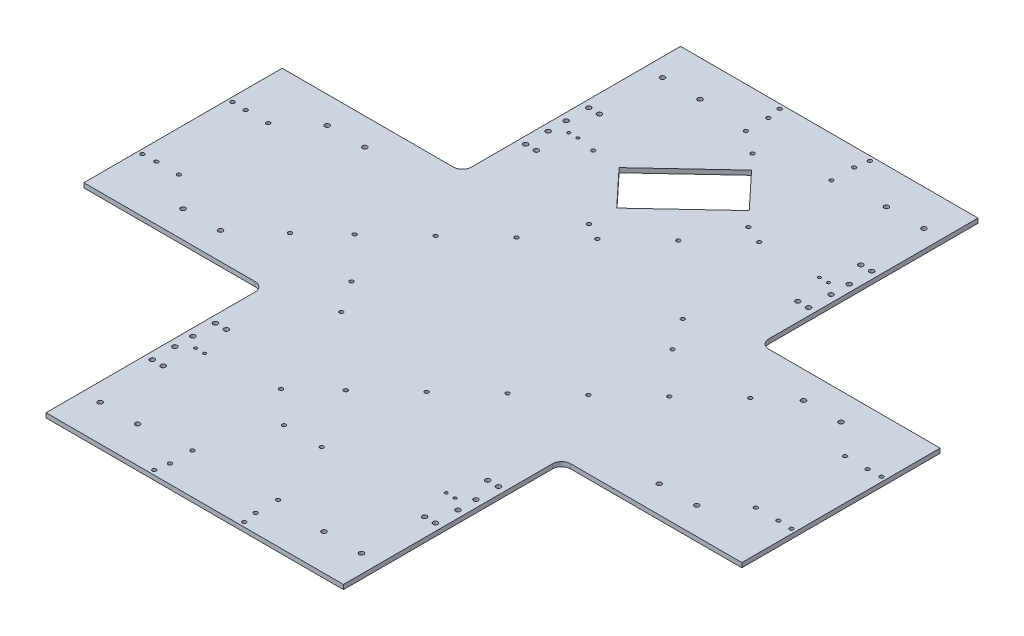
SolidWorks part; units mm, degrees
other "Markup1"
sketch "Sketch8"
material "3.0205 (EN-AW 1200)"
ref_plane "前视基准面" through (0, 0, 0) normal (0, 0, 1) x (1, 0, 0)
ref_plane "上视基准面" through (0, 0, 0) normal (0, 1, 0) x (1, 0, 0)
ref_plane "右视基准面" through (0, 0, 0) normal (1, 0, 0) x (0, 0, -1)
other "Configuration Table"
sketch "Sketch1" plane through (0, 0, 0) normal (0, 1, 0) x (1, 0, 0)
  line L0 (165, 352) -> (-165, 352)
  line L1 (-165, 352) -> (-165, 110)
  line L2 (-165, 110) -> (-365, 110)
  line L5 (-365, 110) -> (-365, -110)
  line L6 (0, 352) -> (0, -66.8675) construction
  line L7 (-365, 0) -> (131.0517, 0) construction
  line L8 (365, 110) -> (365, -110)
  line L11 (165, 110) -> (365, 110)
  line L12 (165, 352) -> (165, 110)
  line L13 (165, -352) -> (165, -110)
  line L14 (165, -110) -> (365, -110)
  line L19 (-165, -110) -> (-365, -110)
  line L20 (-165, -352) -> (-165, -110)
  line L21 (165, -352) -> (-165, -352)
  point P21 (365, 0)
  dimension "D1" = 165
  dimension "D2" = 200
  dimension "D3" = 110
  dimension "D4" = 242
extrude "Boss-Extrude1" add sketch "Sketch1" along normal blind 5
sketch "Sketch2" plane through (0, 5, 0) normal (0, 1, 0) x (1, 0, 0)
  line L3 (365, -110) -> (365, 110) construction
  line L4 (-56.7455, 0) -> (47.5165, 0) construction
  line L5 (0, 54.7142) -> (0, -64.2255) construction
  line L7 (165, 352) -> (-165, 352) construction
  circle A0 centre (345, 49.5) radius 2.125
  circle A1 centre (320, 49.5) radius 2.125
  circle A7 centre (320, -49.5) radius 2.125
  circle A8 centre (345, -49.5) radius 2.125
  circle A9 centre (-345, -49.5) radius 2.125
  circle A10 centre (-320, -49.5) radius 2.125
  circle A13 centre (-320, 49.5) radius 2.125
  circle A14 centre (-345, 49.5) radius 2.125
  circle A15 centre (47.5, 332) radius 2.125
  circle A16 centre (47.5, 307) radius 2.125
  circle A17 centre (-47.5, 307) radius 2.125
  circle A18 centre (-47.5, 332) radius 2.125
  circle A19 centre (-47.5, -332) radius 2.125
  circle A20 centre (-47.5, -307) radius 2.125
  circle A21 centre (47.5, -307) radius 2.125
  circle A22 centre (47.5, -332) radius 2.125
  dimension "D3" = 49.5
  dimension "D5" = 4.25
  dimension "D7" = 4.25
  dimension "D9" = 4.25
  dimension "D10" = 4.25
  dimension "D2" = 47.5
  dimension "D4" = 25
  dimension "D6" = 20
  dimension "20" = 20
  dimension "D13" = 25
extrude "Cut-Extrude1" cut sketch "Sketch2" against normal blind 3
sketch "Sketch4" plane through (0, 5, 0) normal (0, 1, 0) x (1, 0, 0)
  line L0 (-165, 352) -> (-165, 110) construction
  line L1 (165, 352) -> (-165, 352) construction
  line L2 (0, 46.9886) -> (0, -40.2904) construction
  line L3 (-35.103, 0) -> (92.4951, 0) construction
  line L5 (165, -352) -> (165, -110) construction
  circle A0 centre (-157, 172) radius 2.6
  circle A1 centre (-145, 172) radius 2.6
  circle A2 centre (-157, 197) radius 2.6
  circle A3 centre (-157, 217) radius 2.6
  circle A4 centre (-157, 242) radius 2.6
  circle A5 centre (-145, 242) radius 2.6
  circle A6 centre (145, 242) radius 2.6
  circle A7 centre (157, 242) radius 2.6
  circle A8 centre (157, 217) radius 2.6
  circle A9 centre (157, 197) radius 2.6
  circle A10 centre (145, 172) radius 2.6
  circle A11 centre (157, 172) radius 2.6
  circle A12 centre (157, -172) radius 2.6
  circle A13 centre (145, -172) radius 2.6
  circle A14 centre (157, -197) radius 2.6
  circle A15 centre (157, -217) radius 2.6
  circle A16 centre (157, -242) radius 2.6
  circle A17 centre (145, -242) radius 2.6
  circle A18 centre (-145, -242) radius 2.6
  circle A19 centre (-157, -242) radius 2.6
  circle A20 centre (-157, -217) radius 2.6
  circle A21 centre (-157, -197) radius 2.6
  circle A22 centre (-145, -172) radius 2.6
  circle A23 centre (-157, -172) radius 2.6
  circle A24 centre (144, -207) radius 1.6
  circle A25 centre (-144, -207) radius 1.6
  circle A26 centre (144, 207) radius 1.6
  circle A27 centre (-144, 207) radius 1.6
  circle A28 centre (134, -207) radius 1.6
  circle A29 centre (-134, -207) radius 1.6
  circle A30 centre (134, 207) radius 1.6
  circle A31 centre (-134, 207) radius 1.6
  dimension "D3" = 5.2
  dimension "D4" = 5.2
  dimension "D5" = 8
  dimension "D6" = 8
  dimension "D9" = 5.2
  dimension "D10" = 5.2
  dimension "D11" = 5.2
  dimension "D12" = 5.2
  dimension "D19" = 3.2
  dimension "D20" = 21
  dimension "D21" = 10
  dimension "D22" = 3.2
  dimension "D23" = 10
  dimension "D1" = 8
  dimension "D2" = 20
  dimension "D7" = 8
  dimension "D8" = 20
  dimension "D13" = 25
  dimension "D14" = 20
  dimension "D15" = 25
  dimension "D16" = 25
  dimension "D17" = 110
  dimension "D18" = 0
extrude "Cut-Extrude3" cut sketch "Sketch4" against normal blind 10
sketch "Sketch5" plane through (0, 5, 0) normal (0, 1, 0) x (1, 0, 0)
  line L0 (165, 352) -> (-165, 352) construction
  line L5 (-46.9195, 0) -> (66.6223, 0) construction
  line L6 (0, 59.0569) -> (0, -54.4849) construction
  line L10 (-365, 110) -> (-365, -110) construction
  circle A0 centre (-50, 347) radius 2.125
  circle A1 centre (50, 347) radius 2.125
  circle A2 centre (50, -347) radius 2.125
  circle A3 centre (-50, -347) radius 2.125
  circle A4 centre (-360, 50) radius 2.125
  circle A5 centre (-360, -50) radius 2.125
  circle A6 centre (360, -50) radius 2.125
  circle A7 centre (360, 50) radius 2.125
  dimension "D1" = 4.25
  dimension "D2" = 4.25
  dimension "D3" = 50
  dimension "D6" = 4.25
  dimension "D7" = 4.25
  dimension "5" = 5
  dimension "D4" = 50
  dimension "D5" = 50
  dimension "D8" = 50
  dimension "D9" = 5
  dimension "D10" = 5
extrude "Cut-Extrude4" cut sketch "Sketch5" against normal blind 10
fillet "Fillet1" radius 10 4 edges at (-165, 2.5, -110) (-165, 2.5, 110) (165, 2.5, 110) (165, 2.5, -110)
sketch "Sketch6" plane through (0, 5, 0) normal (0, 1, 0) x (1, 0, 0)
  line L0 (165, 352) -> (-165, 352) construction
  line L1 (-165, 352) -> (-165, 120) construction
  line L3 (0, 50.3702) -> (0, -42.7646) construction
  line L4 (-54.8568, 0) -> (91.2004, 0) construction
  line L5 (365, 110) -> (175, 110) construction
  line L6 (365, -110) -> (365, 110) construction
  circle A0 centre (-145, 312) radius 2.6
  circle A1 centre (-103.4, 312) radius 2.6
  circle A4 centre (103.4, 312) radius 2.6
  circle A5 centre (145, 312) radius 2.6
  circle A6 centre (145, -312) radius 2.6
  circle A7 centre (103.4, -312) radius 2.6
  circle A8 centre (-103.4, -312) radius 2.6
  circle A9 centre (-145, -312) radius 2.6
  circle A10 centre (243.4, 80) radius 2.6
  circle A11 centre (285, 80) radius 2.6
  circle A12 centre (285, -80) radius 2.6
  circle A13 centre (243.4, -80) radius 2.6
  circle A14 centre (-243.4, -80) radius 2.6
  circle A15 centre (-285, -80) radius 2.6
  circle A16 centre (-285, 80) radius 2.6
  circle A17 centre (-243.4, 80) radius 2.6
  dimension "D1" = 5.2
  dimension "D2" = 5.2
  dimension "D3" = 5.2
  dimension "D4" = 5.2
  dimension "D5" = 40
  dimension "D8" = 30
  dimension "D6" = 20
  dimension "D7" = 41.6
  dimension "D9" = 80
  dimension "D10" = 41.6
extrude "Cut-Extrude5" cut sketch "Sketch6" against normal blind 10
sketch "Sketch7" plane through (0, 5, 0) normal (0, 1, 0) x (1, 0, 0)
  line L0 (164.5832, 153.9982) -> (-155.4181, -145.4226) construction
  line L1 (165, 299.5544) -> (-272.7048, -110) construction
  line L2 (165, 120) -> (165, 352) construction
  line L3 (-365, -110) -> (-175, -110) construction
  line L4 (272.7048, 110) -> (-165, -299.5544) construction
  line L5 (365, 110) -> (175, 110) construction
  line L6 (-165, -120) -> (-165, -352) construction
  line L7 (-268.9942, -53.3124) -> (-51.1439, -286.1364) construction
  line L8 (84.7791, 253.9237) -> (328.5288, -6.5799) construction
  line L9 (-72.423, 77.401) -> (72.423, -77.401) construction
  line L11 (-380.0049, -355.5654) -> (380.0049, -355.5654) construction
  line L12 (-380.0049, -355.5654) -> (-380.0049, 355.5654) construction
  line L13 (-380.0049, 355.5654) -> (380.0049, 355.5654) construction
  line L14 (380.0049, -355.5654) -> (380.0049, 355.5654) construction
  line L15 (-380.0049, -355.5654) -> (380.0049, 355.5654) construction
  line L16 (-380.0049, 355.5654) -> (380.0049, -355.5654) construction
  circle A4 centre (-72.423, 77.401) radius 2.125
  circle A5 centre (-26.0555, 120.7864) radius 2.125
  circle A6 centre (20.3121, 164.1719) radius 2.125
  circle A7 centre (66.6796, 207.5574) radius 2.125
  circle A8 centre (-118.7906, 34.0155) radius 2.125
  circle A9 centre (-165.1581, -9.37) radius 2.125
  circle A10 centre (-202.2522, -44.0784) radius 2.125
  circle A11 centre (-57.4061, -198.8803) radius 2.125
  circle A12 centre (-20.3121, -164.1719) radius 2.125
  circle A13 centre (26.0555, -120.7864) radius 2.125
  circle A14 centre (211.5257, 52.7555) radius 2.125
  circle A15 centre (165.1581, 9.37) radius 2.125
  circle A16 centre (118.7906, -34.0155) radius 2.125
  circle A17 centre (72.423, -77.401) radius 2.125
  point P53 (0, 0)
  dimension "D6" = 4.25
  dimension "D7" = 4.25
  dimension "D8" = 4.25
  dimension "D9" = 4.25
  dimension "D10" = 4.25
  dimension "D11" = 4.25
  dimension "D12" = 4.25
  dimension "D1" = 106
  dimension "D3" = 20
  dimension "D4" = 20
  dimension "D5" = 0
  dimension "D13" = 63.5
  dimension "D14" = 63.5
  dimension "D15" = 50.8
  dimension "D16" = 63.5
  dimension "D17" = 63.5
  dimension "D18" = 63.5
extrude "Cut-Extrude6" cut sketch "Sketch7" against normal blind 10
sketch "Sketch9" plane through (0, 5, 0) normal (0, 1, 0) x (1, 0, 0)
  line L0 (167.9289, 112.9289) -> (-167.9289, -112.9289) construction
  line L1 (80.349, 117.7232) -> (149.9169, 14.2734) construction
  line L2 (-142.2885, -25.6171) -> (-87.1446, -107.6179) construction
  line L3 (0, 45.0584) -> (0, -52.9183) construction
  line L4 (-44.6513, 0) -> (48.0404, 0) construction
  line L5 (165, 352) -> (-165, 352) construction
  arc A0 (165, 120) -> (175, 110) centre (175, 120) ccw construction
  arc A1 (-165, -120) -> (-175, -110) centre (-175, -120) ccw construction
  circle A2 centre (-121.5605, -56.4403) radius 2.1
  circle A3 centre (-98.123, -91.2926) radius 2.1
  circle A4 centre (98.123, 91.2926) radius 2.1
  circle A5 centre (121.5605, 56.4403) radius 2.1
  circle A7 centre (21, 232) radius 2.1
  circle A8 centre (-21, 232) radius 2.1
  circle A9 centre (-21, -232) radius 2.1
  circle A10 centre (21, -232) radius 2.1
  dimension "D3" = 4.2
  dimension "D4" = 4.2
  dimension "D5" = 4.2
  dimension "D6" = 4.2
  dimension "D11" = 120
  dimension "D12" = 4.2
  dimension "D1" = 70
  dimension "D2" = 70
  dimension "D7" = 21
  dimension "D8" = 21
  dimension "D9" = 21
  dimension "D10" = 21
  dimension "D13" = 21
extrude "Cut-Extrude7" cut sketch "Sketch9" against normal blind 10
sketch "Sketch10" plane through (0, 5, 0) normal (0, 1, 0) x (1, 0, 0)
  line L0 (70.1652, 238.2086) -> (-130.5354, 50.4158) construction
  line L5 (-6.3046, 303.6061) -> (-217.4253, 106.0633) construction
  line L6 (66.6796, 207.5574) -> (-72.423, 77.401) construction
  line L7 (46.2747, 215.8546) -> (-22.0489, 288.8744) construction
  line L8 (-45, 130.4501) -> (-113.3236, 203.4699) construction
  line L9 (165, 120) -> (165, 352) construction
  line L10 (-114.9608, 133.4634) -> (31.7887, 270.7749) construction
  line L11 (-6.6761, 272.4449) -> (30.9019, 232.2841)
  line L12 (30.9019, 232.2841) -> (-45.0387, 161.2275)
  line L13 (-45.0387, 161.2275) -> (-82.6166, 201.3884)
  line L14 (-82.6166, 201.3884) -> (-6.6761, 272.4449)
  circle A0 centre (46.2747, 215.8546) radius 2.125
  circle A1 centre (-45, 130.4501) radius 2.125
  circle A3 centre (-113.3236, 203.4699) radius 2.125
  circle A4 centre (-22.0489, 288.8744) radius 2.125
  dimension "D3" = 4.25
  dimension "D4" = 4.25
  dimension "D7" = 4.25
  dimension "D8" = 4.25
  dimension "D1" = 20
  dimension "D2" = 100
  dimension "D5" = 210
  dimension "D6" = 125
  dimension "D9" = 50
  dimension "D10" = 55
  dimension "D11" = 27.5
  dimension "D12" = 104
extrude "Cut-Extrude8" cut sketch "Sketch10" against normal blind 10
